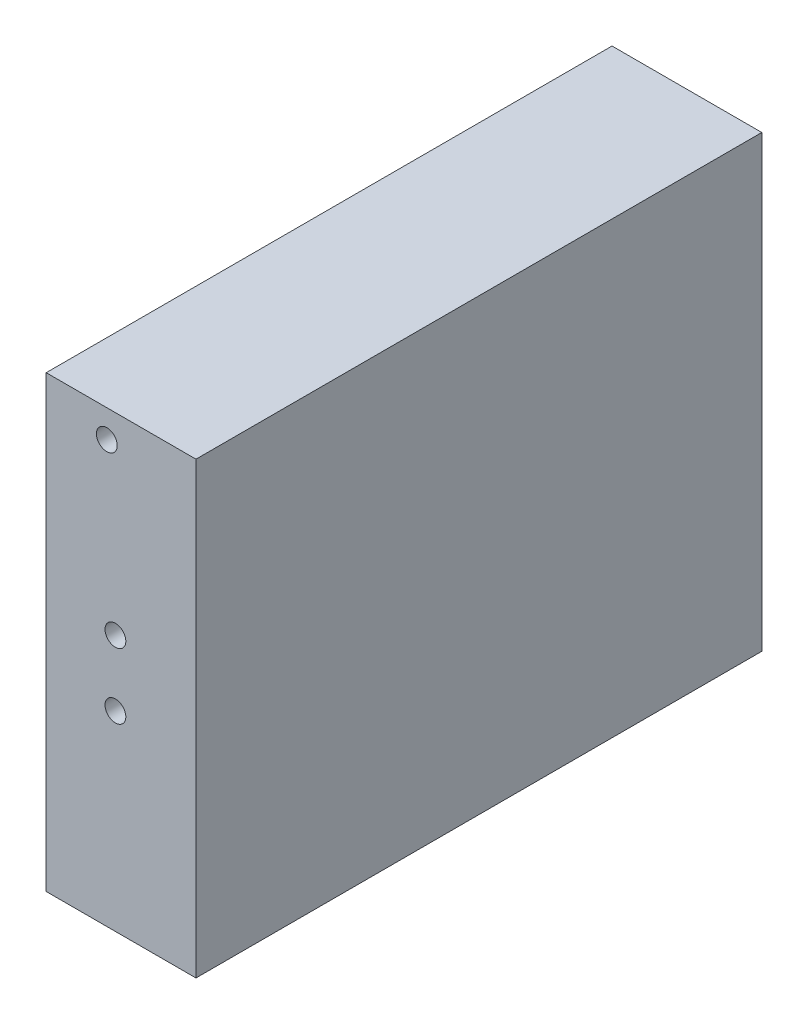
SolidWorks part; units mm, degrees
ref_plane "Front Plane" through (0, 0, 0) normal (0, 0, 1) x (1, 0, 0)
ref_plane "Top Plane" through (0, 0, 0) normal (0, 1, 0) x (1, 0, 0)
ref_plane "Right Plane" through (0, 0, 0) normal (1, 0, 0) x (0, 0, -1)
sketch "Sketch1" plane through (0, 0, 0) normal (0, 0, 1) x (1, 0, 0)
  line L1 (0, 0) -> (57.15, 0)
  line L2 (0, 0) -> (0, 171.45)
  line L3 (0, 171.45) -> (57.15, 171.45)
  line L4 (57.15, 0) -> (57.15, 171.45)
  dimension "D1" = 57.15
  dimension "D2" = 171.45
extrude "Boss-Extrude1" add sketch "Sketch1" along normal blind 215.9
sketch "Sketch2" plane through (0, 0, 0) normal (0, 0, -1) x (-1, 0, 0)
  circle A0 centre (-24.41, 70.569) radius 3.175 construction
  circle A1 centre (-24.41, 70.569) radius 3.175
extrude "Cut-Extrude1" cut sketch "Sketch2" against normal blind 46.74 contours A1
sketch "Sketch3" plane through (0, 0, 0) normal (0, 0, -1) x (-1, 0, 0)
  circle A0 centre (-24.41, 70.569) radius 3.9687 construction
  circle A1 centre (-24.41, 70.569) radius 3.9687
extrude "Cut-Extrude2" cut sketch "Sketch3" against normal blind 13.04 contours A1
sketch "Sketch4" plane through (0, 0, 215.9) normal (0, 0, 1) x (1, 0, 0)
  circle A1 centre (26.41, 73.569) radius 3.175 construction
  circle A2 centre (26.41, 98.569) radius 3.175 construction
  circle A4 centre (26.41, 73.569) radius 3.175
  circle A5 centre (26.41, 98.569) radius 3.175
extrude "Cut-Extrude3" cut sketch "Sketch4" against normal blind 35.16 contours A5 | A4
sketch "Sketch5" plane through (0, 0, 215.9) normal (0, 0, 1) x (1, 0, 0)
  circle A0 centre (23.13, 10.569) radius 3.175 construction
  circle A1 centre (23.13, 10.569) radius 3.175
extrude "Cut-Extrude4" cut sketch "Sketch5" against normal blind 94.66 contours A1
sketch "Sketch6" plane through (0, 0, 215.9) normal (0, 0, 1) x (1, 0, 0)
  circle A0 centre (26.41, 73.569) radius 3.9687 construction
  circle A1 centre (26.41, 98.569) radius 3.9687 construction
  circle A2 centre (26.41, 73.569) radius 3.9687
  circle A3 centre (26.41, 98.569) radius 3.9687
extrude "Cut-Extrude5" cut sketch "Sketch6" against normal blind 10.16 contours A3 | A2
sketch "Sketch7" plane through (0, 0, 215.9) normal (0, 0, 1) x (1, 0, 0)
  circle A0 centre (23.13, 10.569) radius 3.9687 construction
  circle A1 centre (23.13, 10.569) radius 3.9687
extrude "Cut-Extrude6" cut sketch "Sketch7" against normal blind 69.66 contours A1
sketch "Sketch8" plane through (0, 0, 0) normal (0, 0, -1) x (-1, 0, 0)
  point P0 (-57.15, 171.45)
mirror "Mirror1" about plane through (0, 0, 215.9) normal (0, 1, 0) of bodies 107
delete or keep bodies "Body-Delete/Keep 1" type keep bodies bodies 108
sketch "Sketch9" plane through (0, 0, 0) normal (0, 0, -1) x (-1, 0, 0)
  point P0 (-57.15, -171.45)
